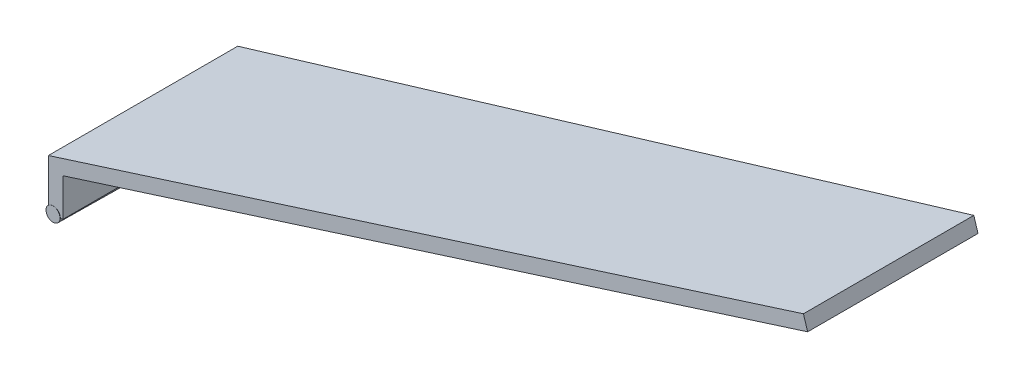
SolidWorks part; units mm, degrees
ref_plane "Płaszczyzna przednia" through (0, 0, 0) normal (0, 0, 1) x (1, 0, 0)
ref_plane "Płaszczyzna górna" through (0, 0, 0) normal (0, 1, 0) x (1, 0, 0)
ref_plane "Płaszczyzna prawa" through (0, 0, 0) normal (1, 0, 0) x (0, 0, -1)
ref_plane "Płaszczyzna1" through (0, 0, -1.9962) normal (0, 0, -1) x (-1, 0, 0)
sketch "Szkic1" plane through (0, 0, -1.9962) normal (0, 0, -1) x (-1, 0, 0)
  line L0 (-17.0283, 0.8) -> (0.3, 0.8)
  line L1 (0.3, 0.8) -> (0.3, 1.0211)
  line L2 (0.3, 1.0211) -> (-15.4483, 5.9)
  line L3 (-15.4483, 5.9) -> (-17.0283, 0.8)
extrude "Dodanie-wyciągnięcie1" add sketch "Szkic1" against normal blind 3.9924
sketch "Szkic2" plane through (0, 0.8, 0) normal (0, -1, 0) x (1, 0, 0)
  line L0 (-0.3, 1.9962) -> (0, 1.9962)
  line L1 (0, 1.9962) -> (0, -1.9962)
  line L2 (0, -1.9962) -> (-0.3, -1.9962)
  line L3 (-0.3, -1.9962) -> (-0.3, 1.9962)
extrude "Dodanie-wyciągnięcie2" add sketch "Szkic2" along normal blind 0.8
draft "Pochylenie1" type of draft neutral plane draft angle 17.213 faces to draft 1 face at (12.7712, 0.8, -0.499) neutral plane through (0, 0, 1.9962) neutral plane normal (1, 0, 0) parameters "D1"=17.213
draft "Pochylenie2" type of draft neutral plane draft angle 0.728 faces to draft 2 face at (5.0642, 2.2224, -1.9962) face at (5.0642, 2.2224, 1.9962) neutral plane through (0, 0, 1.9962) neutral plane normal (1, 0, 0) parameters "D1"=0.728
sketch "Szkic9" plane through (0.0253, 0, -1.9959) normal (0.0127, 0, -0.9999) x (-0.9999, 0, -0.0127)
  line L0 (0.3254, 0) -> (0.0253, 0) construction
  circle A0 centre (0.1754, 0) radius 0.15
extrude "Dodanie-wyciągnięcie3" add sketch "Szkic9" against normal blind 4
